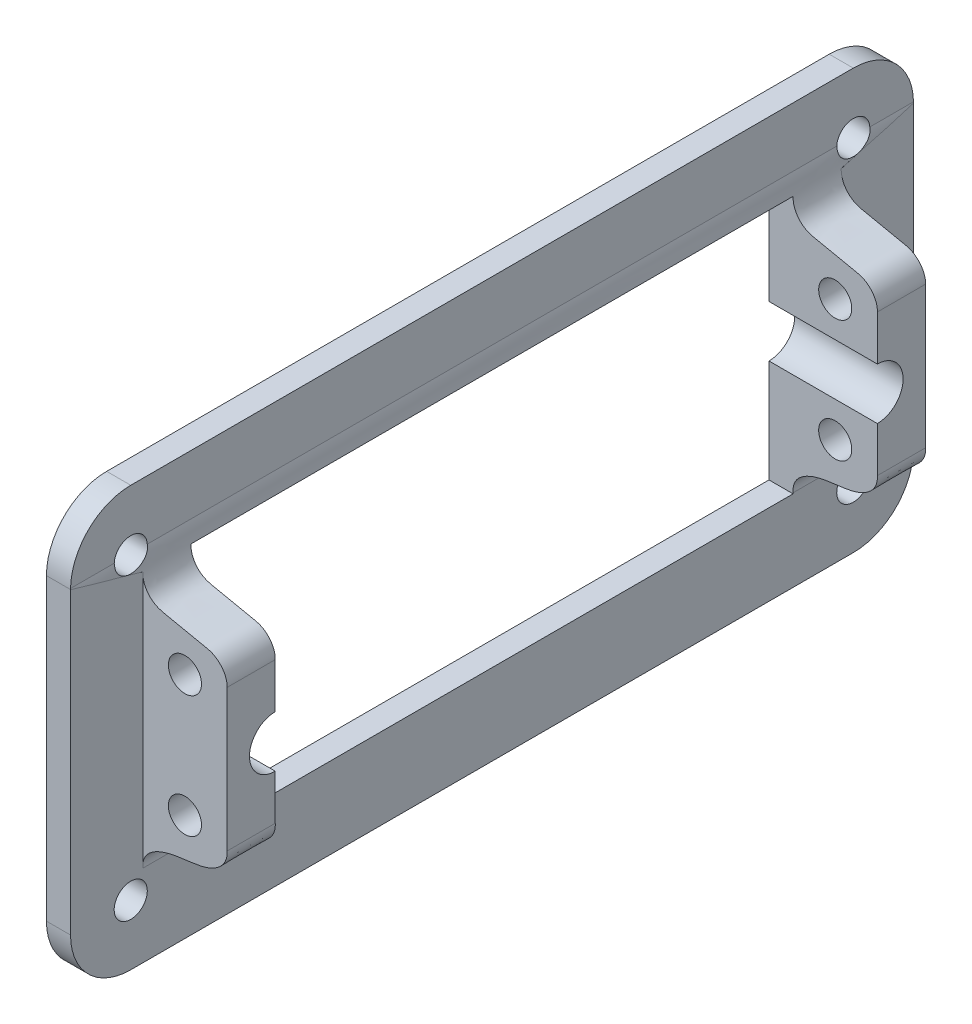
SolidWorks part; units mm, degrees
ref_plane "Front Plane" through (0, 0, 0) normal (0, 0, 1) x (1, 0, 0)
ref_plane "Top Plane" through (0, 0, 0) normal (0, 1, 0) x (1, 0, 0)
ref_plane "Right Plane" through (0, 0, 0) normal (1, 0, 0) x (0, 0, -1)
sketch "Sketch1" plane through (0, 0, 0) normal (0, 0, 1) x (1, 0, 0)
  line L0 (0, 34.8462) -> (4, 34.8462)
  line L1 (4, 34.8462) -> (4, 25)
  line L2 (0, 34.8462) -> (0, -34.8462)
  line L3 (0, -34.8462) -> (4, -34.8462)
  line L4 (4, -34.8462) -> (4, -21.2337)
  line L5 (18, 11.7663) -> (18, -11.7663)
  arc A0 (11, 12.875) -> (13.7082, 9.6475) centre (11, 10.125) ccw
  arc A1 (11, 12.875) -> (13.7082, 9.6475) centre (11, 10.125) cw
  arc A2 (11, -7.375) -> (13.5842, -11.0655) centre (11, -10.125) cw
  arc A3 (11, -7.375) -> (13.5842, -11.0655) centre (11, -10.125) ccw
  spline S0 degree 3 poles (18, -11.7663) (18.1149, -13.5472) (15.7002, -16.006) (11.1966, -16.4378) (6.6623, -17.1147) (3.8482, -19.1062) (4, -21.2337) knots 0 0 0 0 0.252595 0.500732 0.712369 1 1 1 1
  spline S1 degree 3 poles (4, 25) (4.2857, 23.3856) (3.3342, 20.5303) (5.8694, 17.4016) (8.5978, 17.0496) (11.2452, 16.4433) (13.4449, 15.9435) (16.5284, 15.432) (18.0711, 13.3589) (18, 11.7663) knots 0 0 0 0 0.228848 0.34828 0.486981 0.584133 0.715565 0.79023 1 1 1 1
  dimension "D1" = 2.75
  dimension "D2" = 4
  dimension "D3" = 4.2289
  dimension "D4" = 4.8893
  dimension "D5" = 5.9058
  dimension "D6" = 7.1619
  dimension "D7" = 8.8784
  dimension "D8" = 11
  dimension "D9" = 13.5842
  dimension "D10" = 13.7082
  dimension "D11" = 13.8702
  dimension "D12" = 15.4876
  dimension "D13" = 17.1107
  dimension "D14" = 17.4912
  dimension "D15" = 18
  dimension "D16" = 9.6475
  dimension "D17" = 7.375
  dimension "D18" = 11.7663
  dimension "D19" = 16.5
  dimension "D20" = 13.7187
  dimension "D21" = 15.4794
  dimension "D22" = 15.885
  dimension "D23" = 16.5
  dimension "D24" = 16.9546
  dimension "D25" = 17.8257
  dimension "D26" = 19.9
  dimension "D27" = 22.2918
  dimension "D28" = 25
  dimension "D29" = 34.8462
  dimension "D33" = 11.7663
  dimension "D34" = 14.2811
  dimension "D35" = 15.4794
  dimension "D37" = 17.3224
  dimension "D38" = 18.719
  dimension "D39" = 21.2337
  dimension "D40" = 34.8462
extrude "Boss-Extrude1" add sketch "Sketch1" against normal blind 140
sketch "Sketch3" plane through (0, 0, 0) normal (1, 0, 0) x (0, 0, -1)
  line L0 (10, 34.8462) -> (130.0439, 34.8462)
  line L1 (0, 24.8462) -> (0, -24.8462)
  line L2 (140, 24.8462) -> (140, -24.8462)
  line L3 (10, -34.8462) -> (130.0439, -34.8462)
  line L4 (0, 24.8462) -> (12, 21.3875)
  line L5 (20, 21.3875) -> (120, 21.3875)
  line L6 (20, 21.3875) -> (20, -21.3875)
  line L7 (20, -21.3875) -> (120, -21.3875)
  line L8 (120, 21.3875) -> (120, -21.3875)
  line L9 (12, 21.3875) -> (12, -21.3875)
  line L10 (12, -21.3875) -> (0, -24.8462)
  line L11 (128, 21.3875) -> (140, 24.8462)
  line L12 (128, 21.3875) -> (128, -21.3875)
  line L13 (128, -21.3875) -> (140, -24.8462)
  line L14 (128, -21.3875) -> (58.4731, -21.6228)
  line L15 (140, -24.8462) -> (139.6344, -25.287)
  line L17 (140, 34.8462) -> (0, 34.8462) construction
  line L18 (140, 34.8462) -> (140, -34.8462) construction
  arc A0 (140, -24.8462) -> (130.0439, -34.8462) centre (129.9999, -24.8462) cw
  arc A1 (130.0439, 34.8462) -> (140, 24.8462) centre (129.9999, 24.8462) cw
  arc A2 (10, 34.8462) -> (0, 24.8462) centre (10, 24.8462) ccw
  arc A3 (0, -24.8462) -> (10, -34.8462) centre (10, -24.8462) ccw
  arc A4 (20, 4.2788) -> (20, -4.2788) centre (20, 0) ccw
  arc A5 (120, -4.2788) -> (120, 4.2788) centre (120, 0) ccw
  circle A6 centre (10, 24.8462) radius 2.75
  circle A7 centre (129.9999, 24.8462) radius 2.7501
  circle A8 centre (10, -24.8462) radius 2.75
  circle A9 centre (129.9999, -24.8462) radius 2.7501
  dimension "D3" = 5.5003
  dimension "D4" = 5.5
  dimension "D5" = 5.5002
  dimension "D6" = 10.0001
  dimension "D7" = 10
  dimension "D8" = 58.4731
  dimension "D9" = 21.3875
  dimension "D10" = 21.6228
  dimension "D11" = 4.2788
  dimension "D1" = 8
  dimension "D2" = 8
extrude "Cut-Extrude2" cut sketch "Sketch3" along normal through all contours L12 L13 L11 | L10 L9 L4 L1 | L8 A5 | L6 A4 | L8 L5 L6 L7 | A8 | A9 | A6 | A7 region at (0, 0, -5.8504) region at (0, 0, -134.1496) region at (0, 0, -70) region at (0, 0, -18.184) region at (0, 0, -121.816)
extrude "Boss-Extrude2" add sketch "Sketch3<3>" along normal blind 4 contours L12 L13 L11 | L10 L9 L4 L1 region at (0, 0, -5.8504) region at (0, 0, -134.1496)
sketch "Sketch3<3>" plane through (0, 0, 0) normal (1, 0, 0) x (0, 0, -1) same geometry as "Sketch3"
fillet "Fillet1" radius 10 4 edges at (2, 34.8462, 0) (2, -34.8462, -140) (2, 34.8462, -140) (2, -34.8462, 0)
